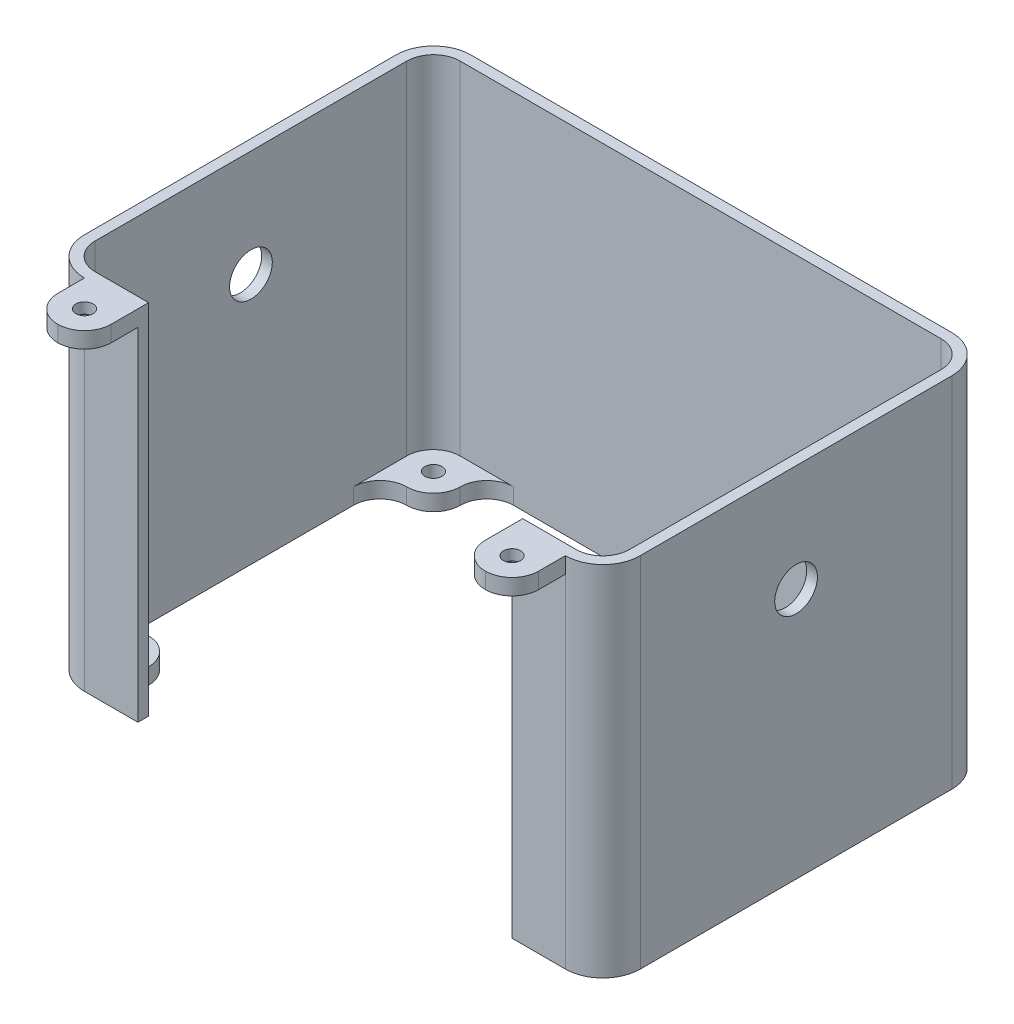
SolidWorks part; units mm, degrees
ref_plane "Front Plane" through (0, 0, 0) normal (0, 0, 1) x (1, 0, 0)
ref_plane "Top Plane" through (0, 0, 0) normal (0, 1, 0) x (1, 0, 0)
ref_plane "Right Plane" through (0, 0, 0) normal (1, 0, 0) x (0, 0, -1)
sketch "Sketch1" plane through (0, 0, 0) normal (0, 1, 0) x (1, 0, 0)
  line L0 (0, -7) -> (45, -7)
  line L1 (0, -5) -> (45, -5)
  line L2 (-7, 0) -> (-7, 29.15)
  line L3 (-5, 0) -> (-5, 29.15)
  line L34 (45, -5) -> (45, -7)
  line L35 (-7, 29.15) -> (-5, 29.15)
  arc A0 (-5, 0) -> (0, -5) centre (0, 0) ccw
  circle A1 centre (0, 0) radius 1.6
  arc A2 (-7, 0) -> (0, -7) centre (0, 0) ccw
  arc A3 (5, 0) -> (10, -5) centre (10, 0) ccw
  arc A4 (-5, 10) -> (0, 5) centre (0, 10) ccw
  arc A5 (5, 0) -> (0, 5) centre (0, 0) ccw
  dimension "D1" = 3.2
  dimension "D2" = 10
  dimension "D3" = 2
  dimension "D4" = 5
  dimension "D5" = 5
  dimension "D6" = 5
  dimension "D7" = 5
  dimension "D8" = 45
  dimension "D9" = 2
  dimension "D10" = 2
  dimension "D11" = 29.15
extrude "Boss-Extrude1" add sketch "Sketch1" against normal blind 3 contours A3 A5 A4 L3 A0 L1 A1 | L2 A2 L0 L1 A0 L3 L35 region at (-4.5019, 0, 4.5019) region at (5, 0, 4.7879)
extrude "Boss-Extrude2" add sketch "Sketch1<3>" along normal blind 32 contours L2 A2 L0 L1 A0 L3 L35 region at (-4.5019, 0, 4.5019)
sketch "Sketch1<3>" plane through (0, 0, 0) normal (0, 1, 0) x (1, 0, 0) same geometry as "Sketch1"
ref_plane "Plane1" through (0, 32, 0) normal (0, 1, 0) x (1, 0, 0)
mirror "Mirror2" about plane through (0, 32, 0) normal (0, 1, 0) of "Boss-Extrude2"
mirror "Mirror4" about plane through (45, -3, 0) normal (-1, 0, 0) of bodies 104 105
mirror "Mirror5" about plane through (90, -3, -29.15) normal (0, 0, 1) of bodies 106
ref_plane "Plane2" through (0, 0, -29.15) normal (0, 0, -1) x (-1, 0, 0)
sketch "Sketch2" plane through (0, 0, 7) normal (0, 0, 1) x (1, 0, 0)
  line L0 (0, 64) -> (90, 64) construction
  line L1 (10, 64) -> (10, -3)
  line L2 (0, -3) -> (90, -3) construction
  line L3 (10, -3) -> (80, -3)
  line L4 (80, -3) -> (80, 64)
  line L5 (80, 64) -> (10, 64)
  line L6 (0, -3) -> (0, 64) construction
  line L7 (90, -3) -> (90, 64) construction
  point P8 (0, 0)
  point P10 (77.5937, -3)
  point P11 (76.6256, -3)
  dimension "D1" = 10
  dimension "D2" = 10
extrude "Cut-Extrude1" cut sketch "Sketch2" against normal up to surface (2 mm away) up to face at (45, 15.25, 5)
sketch "Sketch4" plane through (-7, 0, 0) normal (-1, 0, 0) x (0, 0, 1)
  line L0 (0, 64) -> (-58.3, 64) construction
  circle A0 centre (-29.15, 44) radius 4
  point P6 (-35.6278, 44.042)
  dimension "D1" = 8
  dimension "D2" = 20
  dimension "D3" = 29.15
extrude "Cut-Extrude2" cut sketch "Sketch4" against normal through all
sketch "Sketch10" plane through (0, 64, 0) normal (0, 1, 0) x (1, 0, 0)
  line L0 (0, -7) -> (10, -7)
  line L1 (0, -7) -> (0, -17)
  line L2 (10, -7) -> (10, -17)
  line L3 (0, -17) -> (10, -17)
  line L4 (90, -7) -> (80, -7)
  line L5 (90, -7) -> (90, -17)
  line L6 (80, -7) -> (80, -17)
  line L7 (90, -17) -> (80, -17)
  line L8 (0, -7) -> (10, -17) construction
  line L9 (80, -7) -> (90, -17) construction
  circle A0 centre (5, -12) radius 1.6
  circle A1 centre (85, -12) radius 1.6
  dimension "D1" = 3.2
extrude "Boss-Extrude3" add sketch "Sketch10" against normal blind 3
fillet "Fillet1" radius 5 4 edges at (0, 62.5, 17) (10, 62.5, 17) (90, 62.5, 17) (80, 62.5, 17)
sketch "Sketch11" plane through (0, 61, 0) normal (0, -1, 0) x (1, 0, 0)
  line L1 (8.2909, 12) -> (6.6454, 14.85)
  line L2 (6.6454, 14.85) -> (3.3546, 14.85)
  line L3 (3.3546, 14.85) -> (1.7091, 12)
  line L4 (1.7091, 12) -> (3.3546, 9.15)
  line L5 (3.3546, 9.15) -> (6.6454, 9.15)
  line L6 (6.6454, 9.15) -> (8.2909, 12)
  line L7 (88.2909, 12) -> (86.6454, 14.85)
  line L8 (86.6454, 14.85) -> (83.3546, 14.85)
  line L9 (83.3546, 14.85) -> (81.7091, 12)
  line L10 (81.7091, 12) -> (83.3546, 9.15)
  line L11 (83.3546, 9.15) -> (86.6454, 9.15)
  line L12 (86.6454, 9.15) -> (88.2909, 12)
  circle A0 centre (5, 12) radius 2.85 construction
  circle A1 centre (85, 12) radius 2.85 construction
  dimension "D1" = 5.7
extrude "Cut-Extrude5" cut sketch "Sketch11" against normal blind 1
